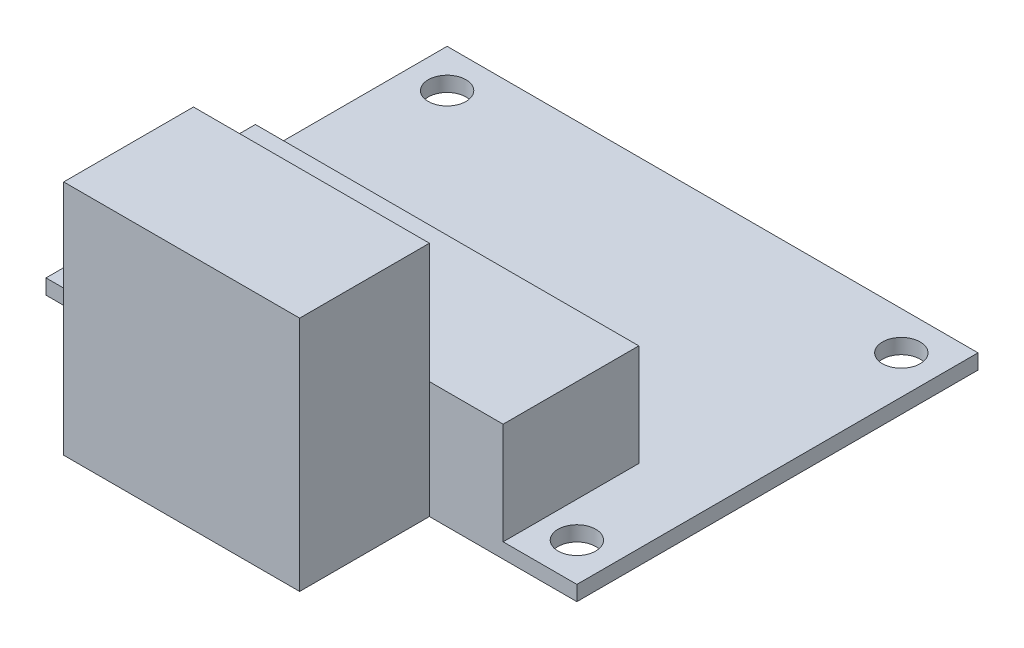
SolidWorks part; units mm, degrees
ref_plane "Front Plane" through (0, 0, 0) normal (0, 0, 1) x (1, 0, 0)
ref_plane "Top Plane" through (0, 0, 0) normal (0, 1, 0) x (1, 0, 0)
ref_plane "Right Plane" through (0, 0, 0) normal (1, 0, 0) x (0, 0, -1)
sketch "Sketch1" plane through (0, 0, 0) normal (0, 1, 0) x (1, 0, 0)
  line L1 (-22.5, -22.5) -> (22.5, -22.5)
  line L2 (-22.5, -22.5) -> (-22.5, 22.5)
  line L3 (-22.5, 22.5) -> (22.5, 22.5)
  line L4 (22.5, -22.5) -> (22.5, 22.5)
  line L5 (-22.5, -22.5) -> (22.5, 22.5) construction
  line L6 (-22.5, 22.5) -> (22.5, -22.5) construction
  point P0 (0, 0)
  dimension "D1" = 45
extrude "Boss-Extrude1" add sketch "Sketch1" along normal mid plane 20.066
sketch "Sketch2" plane through (0, 10.033, 0) normal (0, 1, 0) x (1, 0, 0)
  line L0 (22.5, 22.5) -> (-22.5, 22.5) construction
  line L1 (22.5, -22.5) -> (10, -22.5)
  line L2 (22.5, -22.5) -> (22.5, -11.5)
  line L3 (22.5, -11.5) -> (10, -11.5)
  line L4 (10, -22.5) -> (10, -11.5)
  line L5 (22.5, -22.5) -> (22.5, 22.5) construction
  dimension "D1" = 34
  dimension "D2" = 12.5
extrude "Cut-Extrude1" cut sketch "Sketch2" against normal blind 20.066
mirror "Mirror1" about plane through (0, 0, 0) normal (1, 0, 0) of "Cut-Extrude1"
sketch "Sketch3" plane through (0, 10.033, 0) normal (0, 1, 0) x (1, 0, 0)
  line L0 (-22.5, -11.5) -> (-10, -11.5) construction
  line L1 (-16.25, -11.5) -> (16.2486, -11.5)
  line L2 (-16.25, -11.5) -> (-16.25, 0)
  line L3 (-16.25, 0) -> (16.2486, 0)
  line L4 (16.2486, -11.5) -> (16.2486, 0)
  line L5 (-11.0363, 0) -> (11.0363, 0) construction
  line L7 (-22.5, -11.5) -> (22.5, -11.5)
  line L8 (-22.5, -11.5) -> (-22.5, 22.5)
  line L9 (-22.5, 22.5) -> (22.5, 22.5)
  line L10 (22.5, -11.5) -> (22.5, 22.5)
  line M1 (-22.5, -11.5) -> (-10, -11.5)
  line M5 (10, -11.5) -> (22.5, -11.5)
  line M6 (22.5, -11.5) -> (22.5, 22.5)
  line M7 (22.5, 22.5) -> (-22.5, 22.5)
  line M8 (-22.5, 22.5) -> (-22.5, -11.5)
extrude "Cut-Extrude2" cut sketch "Sketch3" against normal blind 18.796 contours L4 L2 L3 M5 M6 M7 M8 M1 region at (0.0002, 10.033, -9.1363)
extrude "Cut-Extrude3" cut sketch "Sketch3<3>" against normal blind 10.16 contours L4 L3 L2 L1 M5 M1 region at (-0.0007, 10.033, 5.75)
sketch "Sketch3<3>" plane through (0, 10.033, 0) normal (0, 1, 0) x (1, 0, 0) same geometry as "Sketch3"
hole_wizard "M3 Clearance Hole1" positions "Sketch5" profile "Sketch6" hole size "M3" standard "ANSI Metric" end condition up to next
sketch "Sketch5" plane through (0, -8.763, 0) normal (0, 1, 0) x (1, 0, 0)
  line L1 (-19.25, 19.25) -> (19.25, 19.25)
  line L2 (-19.25, 19.25) -> (-19.25, -8.25)
  line L3 (-19.25, -8.25) -> (19.25, -8.25)
  line L4 (19.25, 19.25) -> (19.25, -8.25)
  line L5 (-19.25, 5.5) -> (-22.5, 5.5) construction
  line L6 (-22.5, 22.5) -> (-22.5, -11.5) construction
  line L9 (0, 19.25) -> (0, 22.5) construction
  line L10 (22.5, 22.5) -> (-22.5, 22.5) construction
  point P0 (-19.25, 19.25)
  point P2 (-19.25, -8.25)
  point P4 (19.25, -8.25)
  point P6 (19.25, 19.25)
  dimension "D1" = 38.5
  dimension "D2" = 27.5
sketch "Sketch6" plane through (-19.25, -8.763, -19.25) normal (1, 0, 0) x (0, 0, 1)
  line L0 (0, 0) -> (0, 1.27)
  line L1 (0, 1.27) -> (1.6, 1.27)
  line L2 (1.6, 1.27) -> (1.6, 0)
  line L5 (1.6, 0) -> (0, 0)
  line L11 (0, -6.35) -> (0, 107.95) construction
  dimension "Thru Hole Dia." = 3.2
  dimension "Thru Hole Depth" = 1.27
